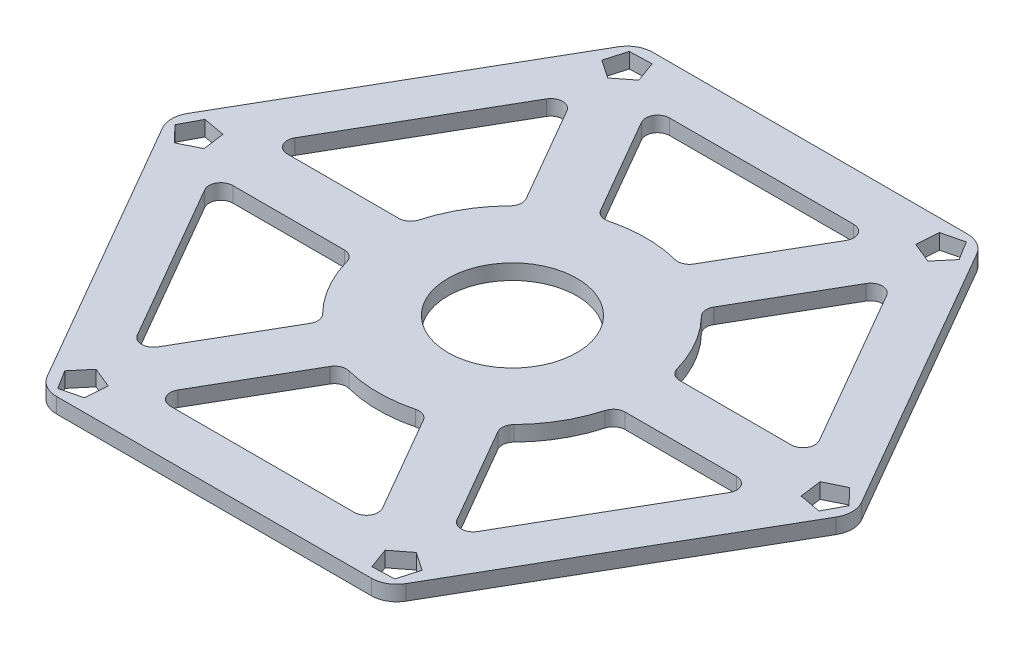
SolidWorks part; units mm, degrees
ref_plane "Front Plane" through (0, 0, 0) normal (0, 0, 1) x (1, 0, 0)
ref_plane "Top Plane" through (0, 0, 0) normal (0, 1, 0) x (1, 0, 0)
ref_plane "Right Plane" through (0, 0, 0) normal (1, 0, 0) x (0, 0, -1)
sketch "Sketch1" plane through (0, 0, 0) normal (0, 1, 0) x (1, 0, 0)
  line L1 (-20.3, 35.1606) -> (-40.6, 0)
  line L2 (-40.6, 0) -> (-20.3, -35.1606)
  line L3 (-20.3, -35.1606) -> (20.3, -35.1606)
  line L4 (20.3, -35.1606) -> (40.6, 0)
  line L5 (40.6, 0) -> (20.3, 35.1606)
  line L6 (20.3, 35.1606) -> (-20.3, 35.1606)
  line L7 (-17, 29.4449) -> (-34, 0)
  line L8 (-34, 0) -> (-17, -29.4449)
  line L9 (-17, -29.4449) -> (17, -29.4449)
  line L10 (17, -29.4449) -> (34, 0)
  line L11 (34, 0) -> (17, 29.4449)
  line L12 (17, 29.4449) -> (-17, 29.4449)
  line L13 (-18.6638, 32.1067) -> (-37.3339, -0.1114) construction
  line L14 (-37.3339, -0.1114) -> (-18.7674, -32.3889) construction
  line L15 (-18.7674, -32.3889) -> (18.5325, -32.4487) construction
  line L16 (18.5325, -32.4487) -> (37.3, 0) construction
  line L17 (37.3, 0) -> (18.6998, 32.1067) construction
  line L18 (18.6998, 32.1067) -> (-18.6638, 32.1067) construction
  line L50 (-17, 29.4449) -> (17, -29.4449) construction
  line L51 (-17, 29.4449) -> (-18.8579, 26.2268)
  line L56 (-13.2841, 29.4449) -> (-17, 29.4449)
  line L57 (-13.3543, 16.6943) -> (-7.7805, 19.9123) construction
  line L58 (-17, 29.4449) -> (-13.2841, 29.4449)
  line L59 (-13.2841, 29.4449) -> (-4.9475, 15.0054)
  line L60 (-17, 29.4449) -> (-18.8579, 26.2268)
  line L61 (-18.8579, 26.2268) -> (-10.5213, 11.7874)
  line L62 (17, 29.4449) -> (13.2841, 29.4449)
  line L63 (13.2841, 29.4449) -> (4.9475, 15.0054)
  line L66 (18.8579, 26.2268) -> (10.5213, 11.7874)
  line L67 (17, 29.4449) -> (18.8579, 26.2268)
  line L68 (34, 0) -> (32.1421, 3.2181)
  line L69 (32.1421, 3.2181) -> (15.4688, 3.2181)
  line L72 (32.1421, -3.2181) -> (15.4688, -3.2181)
  line L73 (34, 0) -> (32.1421, -3.2181)
  line L74 (17, -29.4449) -> (18.8579, -26.2268)
  line L75 (18.8579, -26.2268) -> (10.5213, -11.7874)
  line L78 (13.2841, -29.4449) -> (4.9475, -15.0054)
  line L79 (17, -29.4449) -> (13.2841, -29.4449)
  line L80 (-17, -29.4449) -> (-13.2841, -29.4449)
  line L81 (-13.2841, -29.4449) -> (-4.9475, -15.0054)
  line L84 (-18.8579, -26.2268) -> (-10.5213, -11.7874)
  line L85 (-17, -29.4449) -> (-18.8579, -26.2268)
  line L86 (-34, 0) -> (-32.1421, -3.2181)
  line L87 (-32.1421, -3.2181) -> (-15.4688, -3.2181)
  line L90 (-32.1421, 3.2181) -> (-15.4688, 3.2181)
  line L91 (-34, 0) -> (-32.1421, 3.2181)
  line L104 (-18.6638, 32.1067) -> (-32.712, 27.0191) construction
  line L144 (16.7712, 33.6496) -> (16.5846, 31.0407)
  line L145 (-20.7558, 31.3491) -> (-18.5897, 29.883)
  line L146 (-18.5897, 29.883) -> (-16.5261, 31.49)
  line L147 (-16.5261, 31.49) -> (-17.4167, 33.9493)
  line L148 (-17.4167, 33.9493) -> (-20.0308, 33.8622)
  line L149 (-20.0308, 33.8622) -> (-20.7558, 31.3491)
  line L150 (16.5846, 31.0407) -> (19.0081, 30.057)
  line L151 (19.0081, 30.057) -> (20.6926, 32.0579)
  line L152 (20.6926, 32.0579) -> (19.3101, 34.2783)
  line L153 (19.3101, 34.2783) -> (16.7712, 33.6496)
  line L154 (37.527, 2.3005) -> (35.1743, 1.1577)
  line L155 (35.1743, 1.1577) -> (35.5342, -1.433)
  line L156 (35.5342, -1.433) -> (38.1093, -1.8913)
  line L157 (38.1093, -1.8913) -> (39.3409, 0.4161)
  line L158 (39.3409, 0.4161) -> (37.527, 2.3005)
  line L159 (20.7558, -31.3491) -> (18.5897, -29.883)
  line L160 (18.5897, -29.883) -> (16.5261, -31.49)
  line L161 (16.5261, -31.49) -> (17.4167, -33.9493)
  line L162 (17.4167, -33.9493) -> (20.0308, -33.8622)
  line L163 (20.0308, -33.8622) -> (20.7558, -31.3491)
  line L164 (-16.7712, -33.6496) -> (-16.5846, -31.0407)
  line L165 (-16.5846, -31.0407) -> (-19.0081, -30.057)
  line L166 (-19.0081, -30.057) -> (-20.6926, -32.0579)
  line L167 (-20.6926, -32.0579) -> (-19.3101, -34.2783)
  line L168 (-19.3101, -34.2783) -> (-16.7712, -33.6496)
  line L169 (-37.527, -2.3005) -> (-35.1743, -1.1577)
  line L170 (-35.1743, -1.1577) -> (-35.5342, 1.433)
  line L171 (-35.5342, 1.433) -> (-38.1093, 1.8913)
  line L172 (-38.1093, 1.8913) -> (-39.3409, -0.4161)
  line L173 (-39.3409, -0.4161) -> (-37.527, -2.3005)
  circle A0 centre (0.0529, 0) radius 7.6
  circle A1 centre (-18.6638, 32.1067) radius 1.8 construction
  arc A4 (-10.5213, 11.7874) -> (-15.4688, 3.2181) centre (0, 0) ccw
  arc A5 (4.9475, 15.0054) -> (-4.9475, 15.0054) centre (0, 0) ccw
  arc A6 (15.4688, 3.2181) -> (10.5213, 11.7874) centre (0, 0) ccw
  arc A7 (10.5213, -11.7874) -> (15.4688, -3.2181) centre (0, 0) ccw
  arc A8 (-4.9475, -15.0054) -> (4.9475, -15.0054) centre (0, 0) ccw
  arc A9 (-15.4688, -3.2181) -> (-10.5213, -11.7874) centre (0, 0) ccw
  point P58 (0.0529, 0)
  point P59 (0, -0.1098)
  point P62 (0, 0)
  point P67 (0, 0)
  point P92 (0, 0)
  dimension "D7" = 6
  dimension "D5" = 40
  dimension "D6" = 3.6
  dimension "D1" = 40.6
  dimension "D2" = 6.6
  dimension "D3" = 3.3
  dimension "D4" = 6
extrude "Boss-Extrude1" add sketch "Sketch1" along normal blind 1.8 contours L5 L6 L1 L2 L3 L4 L171 L170 L169 L166 L165 L164 L161 L160 L159 L156 L155 L154 L151 L150 L144 L148 L147 L146 L12 L11 L10 L9 | L87 A9 L84 L8 L9 L81 A8 L78 L10 L75 A7 L72 L11 L69 A6 L66 L12 L63 A5 L59 L7 L61 A4 L90 region at (0, 0, -34.0865) region at (-15.1421, 0, -28.5453)
fillet "Fillet1" radius 3 6 edges at (-40.6, 0.9, 0) (-20.3, 0.9, 35.1606) (20.3, 0.9, 35.1606) (40.6, 0.9, 0) (20.3, 0.9, -35.1606) (-20.3, 0.9, -35.1606)
fillet "Fillet2" radius 1.4 24 edges at (-32.1421, 0.9, 3.2181) (-15.4688, 0.9, 3.2181) (-10.5213, 0.9, 11.7874) (-18.8579, 0.9, 26.2268) (-13.2841, 0.9, 29.4449) (13.2841, 0.9, 29.4449) (-4.9475, 0.9, 15.0054) (4.9475, 0.9, 15.0054) (18.8579, 0.9, 26.2268) (10.5213, 0.9, 11.7874) (15.4688, 0.9, 3.2181) (32.1421, 0.9, 3.2181) (32.1421, 0.9, -3.2181) (18.8579, 0.9, -26.2268) (15.4688, 0.9, -3.2181) (10.5213, 0.9, -11.7874) (-32.1421, 0.9, -3.2181) (-15.4688, 0.9, -3.2181) (-4.9475, 0.9, -15.0054) (-13.2841, 0.9, -29.4449) (4.9475, 0.9, -15.0054) (13.2841, 0.9, -29.4449) (-10.5213, 0.9, -11.7874) (-18.8579, 0.9, -26.2268)
ref_plane "Plane1" through (0, 1.8, 0) normal (0, 1, 0) x (1, 0, 0)
scale "Scale1" scale about centroid uniform scaling yes scale factor 1.15
